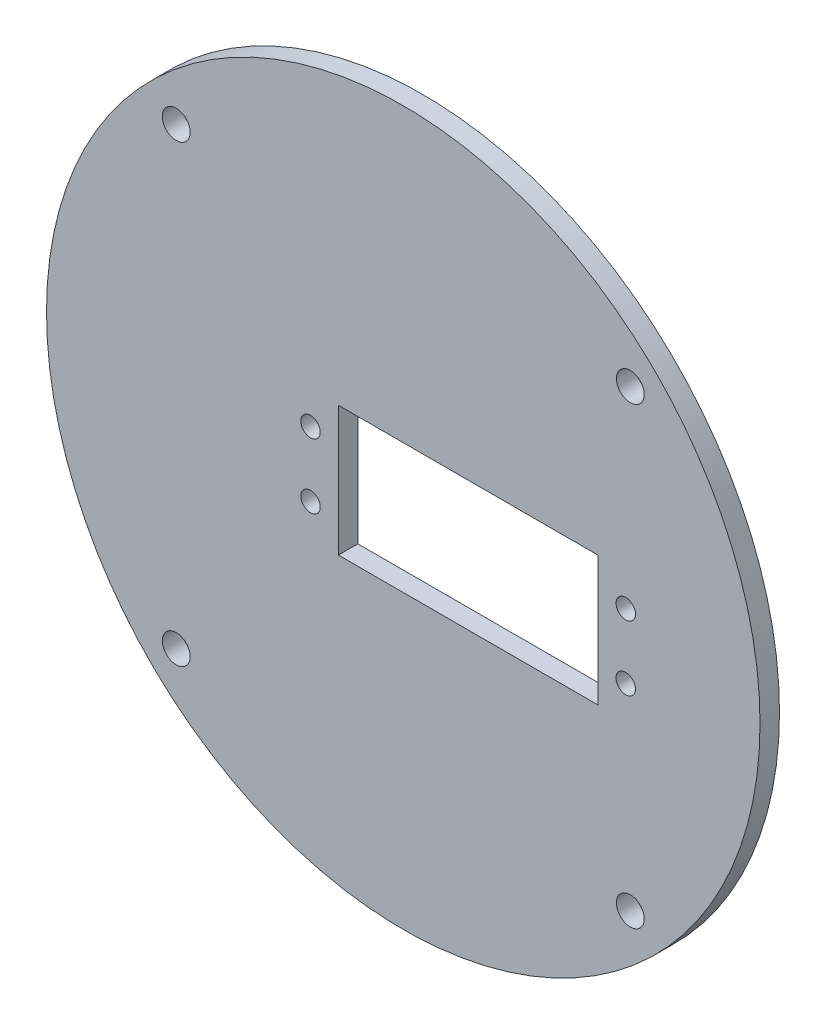
SolidWorks part; units mm, degrees
ref_plane "前视基准面" through (0, 0, 0) normal (0, 0, 1) x (1, 0, 0)
ref_plane "上视基准面" through (0, 0, 0) normal (0, 1, 0) x (1, 0, 0)
ref_plane "右视基准面" through (0, 0, 0) normal (1, 0, 0) x (0, 0, -1)
sketch "草图1" plane through (0, 0, 0) normal (0, 0, 1) x (1, 0, 0)
  line L0 (-35.0018, -35.0018) -> (35.0018, -35.0018)
  line L1 (-35.0018, -35.0018) -> (-35.0018, 35.0018)
  line L2 (-35.0018, 35.0018) -> (35.0018, 35.0018)
  line L3 (35.0018, -35.0018) -> (35.0018, 35.0018)
  line L4 (-35.0018, -35.0018) -> (35.0018, 35.0018) construction
  line L5 (-35.0018, 35.0018) -> (35.0018, -35.0018) construction
  line L7 (-10, 10) -> (30, 10)
  line L8 (-10, 10) -> (-10, -10)
  line L9 (-10, -10) -> (30, -10)
  line L10 (30, 10) -> (30, -10)
  line L11 (-14.3, 5) -> (34.3, 5)
  line L12 (-14.3, 5) -> (-14.3, -5)
  line L13 (-14.3, -5) -> (34.3, -5)
  line L14 (34.3, 5) -> (34.3, -5)
  circle A0 centre (0, 0) radius 55
  circle A1 centre (0, 0) radius 45
  circle A2 centre (-35.0018, 35.0018) radius 2.15
  circle A3 centre (35.0018, 35.0018) radius 2.15
  circle A4 centre (35.0018, -35.0018) radius 2.15
  circle A5 centre (-35.0018, -35.0018) radius 2.15
  circle A6 centre (-14.3, 5) radius 1.5
  circle A7 centre (-14.3, -5) radius 1.5
  circle A8 centre (34.3, 5) radius 1.5
  circle A9 centre (34.3, -5) radius 1.5
  point P16 (-10, 0)
  point P21 (-14.3, 0)
  point P22 (10, 5)
  point P23 (10, 10)
  dimension "D1" = 90
  dimension "D3" = 4.3
  dimension "D4" = 4.3
  dimension "D5" = 4.3
  dimension "D6" = 4.3
  dimension "D7" = 110
  dimension "D14" = 3
  dimension "D15" = 3
  dimension "D16" = 3
  dimension "D17" = 3
  dimension "D2" = 99
  dimension "D9" = 40
  dimension "D10" = 20
  dimension "D11" = 10
  dimension "D12" = 4.3
  dimension "D13" = 10
extrude "凸台-拉伸2" add sketch "草图1" along normal blind 3 contours A0 A5 L1 A1 A2 L2 A3 L3 A4 L0 | L1 A1 | A9 L13 L10 L9 L8 A7 L12 A6 L11 L7 A8 L3 A1 L2 L1 L0 | L2 A1 | A3 L2 A1 L3 | A9 L3 A1 A8 | L0 A1 | A5 L0 A1 L1 | A7 L13 L8 L11 A6 L12 | A2 L1 A1 L2 | A4 L3 A1 L0 | A9 L14 A8 L11 L10 L13 | A9 L3 A8 L14 region at (-32.5805, -32.5805, 0) region at (-31.1198, -31.1198, 0) region at (0, -39.0418, 0) region at (-39.0418, 0, 0) region at (32.5805, -32.5805, 0) region at (-32.5805, 32.5805, 0) region at (39.071, 0, 0) region at (0, 39.0418, 0) region at (32.5805, 32.5805, 0) region at (34.6537, 0, 0) region at (32.0145, 0, 0) region at (-12.0145, 0, 0) region at (-53.4444, 0, 0)
